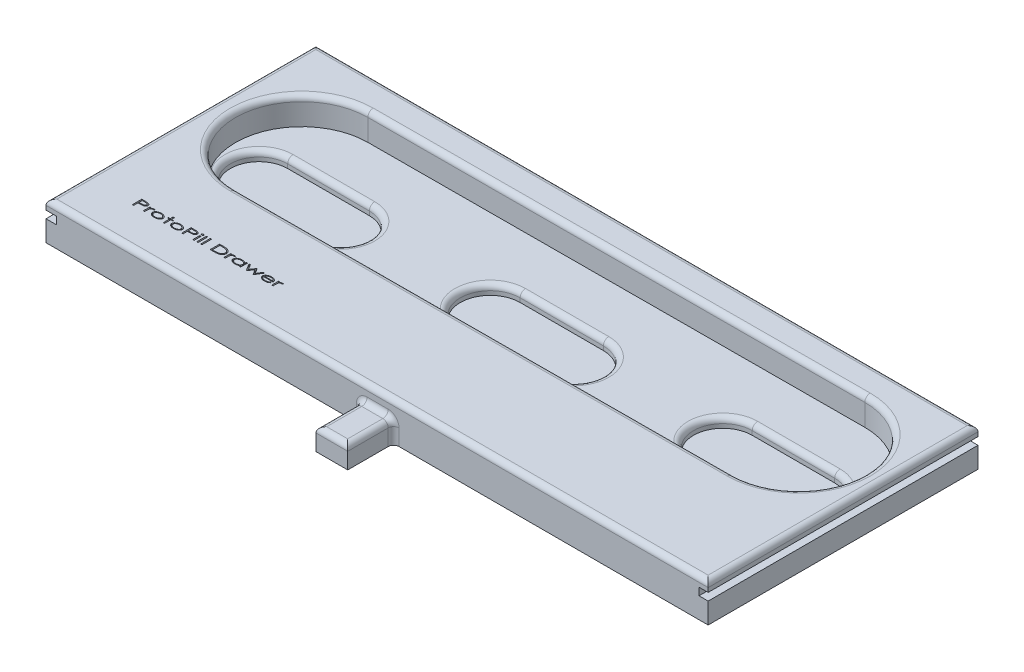
SolidWorks part; units mm, degrees
ref_plane "Front Plane" through (0, 0, 0) normal (0, 0, 1) x (1, 0, 0)
ref_plane "Top Plane" through (0, 0, 0) normal (0, 1, 0) x (1, 0, 0)
ref_plane "Right Plane" through (0, 0, 0) normal (1, 0, 0) x (0, 0, -1)
sketch "Sketch1" plane through (0, 0, 0) normal (0, 1, 0) x (1, 0, 0)
  line L2 (0.7909, -28.3198) -> (245.9852, -28.3198)
  line L4 (245.9852, 64.6802) -> (0.7909, 64.6802)
  line L6 (245.9852, 64.6802) -> (245.9852, -28.3198)
  line L7 (0.7909, 64.6802) -> (0.7909, -28.3198)
  point P0 (0, 0)
  dimension "D2" = 93
extrude "Boss-Extrude1" add sketch "Sketch1" along normal blind 14
sketch "Sketch3" plane through (0, 14, 0) normal (0, 1, 0) x (1, 0, 0)
  line L0 (37.1381, -19.9605) -> (-7.858, -19.9605) construction
  line L2 (37.1381, -19.9605) -> (37.1381, -24.4605) construction
  line L4 (37.1381, -19.9605) -> (123.1941, -19.9579) construction
  line L5 (123.6473, -19.9605) -> (210.1566, -19.9605) construction
  line L6 (210.1566, -19.9605) -> (210.1566, -24.4605) construction
  line L7 (123.6473, -19.9605) -> (123.6473, -24.4605) construction
  line L8 (37.1381, -19.9605) -> (37.1381, 7.1502) construction
  line L9 (123.6473, -19.9605) -> (123.6473, 8.5509) construction
  line L10 (210.1566, -19.9605) -> (210.1566, 7.8884) construction
  line L11 (0.0174, -19.9605) -> (247.1649, -19.9605)
  circle A2 centre (123.7727, -8.9393) radius 11.15
  circle A3 centre (37.3245, -8.6421) radius 11.15
  circle A4 centre (209.8985, -8.6813) radius 11.15
  dimension "D2" = 22.3
  dimension "D3" = 22.3
  dimension "D4" = 22.3
sketch "Sketch2" plane through (0, 0, 28.3198) normal (0, 0, 1) x (1, 0, 0)
  line L0 (0, 10.4529) -> (0, 7.6902)
  line L2 (0, 7.6902) -> (4.6941, 7.6902)
  line L3 (4.6941, 7.6902) -> (4.6941, 10.4529)
  line L5 (4.6941, 10.4529) -> (0, 10.4529)
extrude "Cut-Extrude1" cut sketch "Sketch2" against normal through all
ref_plane "Plane1" through (123.6473, 0, 0) normal (1, 0, 0) x (0, 0, -1)
mirror "Mirror5" about plane through (123.6473, 0, 0) normal (1, 0, 0) of "Cut-Extrude1"
sketch "Sketch7" plane through (0, 0, 28.3198) normal (0, 0, 1) x (1, 0, 0)
  line L0 (123.5912, 14) -> (123.6473, 0) construction
  line L1 (0.0174, 14) -> (247.1649, 14) construction
  line L2 (0.7909, 0) -> (245.9852, 0) construction
  line L3 (123.6473, -7.7) -> (123.6473, 7.7) construction
  line L9 (117.7248, 7.9809) -> (129.5137, 6.0191) construction
  line L10 (117.7248, 6.0191) -> (129.5137, 7.9809) construction
  line L11 (117.7248, 0) -> (129.5137, 0)
  line L12 (117.7248, 0) -> (117.7248, 7.9809)
  line L13 (117.7248, 7.9809) -> (129.5137, 7.9809)
  line L14 (129.5137, 0) -> (129.5137, 7.9809)
  point P8 (123.6193, 7)
extrude "Boss-Extrude2" add sketch "Sketch7" along normal blind 70
sketch "Sketch8" plane through (0, 0, 28.3198) normal (0, 0, 1) x (1, 0, 0)
  line L10 (245.9852, 10.4529) -> (245.9852, 14)
  line L12 (245.9852, 10.4529) -> (245.9852, 14)
  line L14 (245.9852, 14) -> (0.7909, 14)
  line L18 (0.7909, 14) -> (0.7909, 10.4529)
  line L19 (0.7909, 10.4529) -> (4.6941, 10.4529)
  line L20 (4.6941, 10.4529) -> (4.6941, 7.6902)
  line L21 (4.6941, 7.6902) -> (0.7909, 7.6902)
  line L22 (0.7909, 7.6902) -> (0.7909, 0)
  line L23 (0.7909, 0) -> (117.7248, 0)
  line L24 (117.7248, 0) -> (117.7248, 7.9809)
  line L30 (117.7248, 7.9809) -> (129.5137, 7.9809)
  line L31 (117.7248, 7.9809) -> (129.5137, 7.9809)
  line L34 (0.7909, 14) -> (0.7909, 10.4529)
  line L35 (0.7909, 10.4529) -> (4.6941, 10.4529)
  line L36 (4.6941, 10.4529) -> (4.6941, 7.6902)
  line L37 (4.6941, 7.6902) -> (0.7909, 7.6902)
  line L38 (0.7909, 7.6902) -> (0.7909, 0)
  line L39 (0.7909, 0) -> (117.7248, 0)
  line L40 (117.7248, 0) -> (117.7248, 7.9809)
  line L48 (129.5137, 7.9809) -> (129.5137, 0)
  line L49 (129.5137, 7.9809) -> (129.5137, 0)
  line L50 (129.5137, 0) -> (245.9852, 0)
  line L51 (129.5137, 0) -> (245.9852, 0)
  line L52 (245.9852, 0) -> (245.9852, 7.6902)
  line L53 (245.9852, 0) -> (245.9852, 7.6902)
  line L54 (245.9852, 7.6902) -> (242.6006, 7.6902)
  line L55 (245.9852, 7.6902) -> (242.6006, 7.6902)
  line L56 (242.6006, 7.6902) -> (242.6006, 10.4529)
  line L57 (242.6006, 7.6902) -> (242.6006, 10.4529)
  line L58 (242.6006, 10.4529) -> (245.9852, 10.4529)
  line L59 (242.6006, 10.4529) -> (245.9852, 10.4529)
  line L60 (245.9852, 14) -> (0.7909, 14)
  dimension "D1" = 0
extrude "Boss-Extrude3" add sketch "Sketch8" along normal blind 53
sketch "Sketch9" plane through (0, 14, 0) normal (0, 1, 0) x (1, 0, 0)
  line L0 (32.277, -18.0846) -> (215.6701, -17.457) construction
  line L3 (32.193, 6.4621) -> (215.5861, 7.0898)
  line L4 (32.361, -42.6314) -> (215.7541, -42.0037)
  arc A0 (32.193, 6.4621) -> (32.361, -42.6314) centre (32.277, -18.0846) ccw
  arc A1 (215.7541, -42.0037) -> (215.5861, 7.0898) centre (215.6701, -17.457) ccw
  point P6 (123.9735, -17.7708)
extrude "Cut-Extrude2" cut sketch "Sketch9" against normal blind 10
sketch "Sketch10" plane through (0, 4, 0) normal (0, 1, 0) x (1, 0, 0)
  line L0 (22.2559, -23.9029) -> (52.4711, -23.9029) construction
  line L1 (22.2559, -13.2713) -> (52.4711, -13.2713)
  line L2 (22.2559, -34.5345) -> (52.4711, -34.5345)
  line L3 (108.2536, -24.2865) -> (139.0697, -24.2865) construction
  line L4 (108.2536, -13.2003) -> (139.0697, -13.2003)
  line L5 (108.2536, -35.3728) -> (139.0697, -35.3728)
  line L6 (193.8044, -23.6865) -> (224.3383, -23.6865) construction
  line L7 (193.8044, -12.8155) -> (224.3383, -12.8155)
  line L8 (193.8044, -34.5575) -> (224.3383, -34.5575)
  arc A0 (22.2559, -13.2713) -> (22.2559, -34.5345) centre (22.2559, -23.9029) ccw
  arc A1 (52.4711, -34.5345) -> (52.4711, -13.2713) centre (52.4711, -23.9029) ccw
  arc A2 (108.2536, -13.2003) -> (108.2536, -35.3728) centre (108.2536, -24.2865) ccw
  arc A3 (139.0697, -35.3728) -> (139.0697, -13.2003) centre (139.0697, -24.2865) ccw
  arc A4 (193.8044, -12.8155) -> (193.8044, -34.5575) centre (193.8044, -23.6865) ccw
  arc A5 (224.3383, -34.5575) -> (224.3383, -12.8155) centre (224.3383, -23.6865) ccw
  point P2 (37.3635, -23.9029)
  point P9 (123.6616, -24.2865)
  point P16 (209.0714, -23.6865)
extrude "Cut-Extrude4" cut sketch "Sketch10" against normal blind 3.5
fillet "Fillet2" radius 2 4 edges at (240.2169, 14, 17.373) (124.0576, 14, 42.3176) (7.7302, 14, 18.1686) (123.8895, 14, -6.776)
fillet "Fillet3" radius 2 12 edges at (235.2093, 4, 23.6865) (209.0714, 4, 34.5575) (182.9335, 4, 23.6865) (150.1559, 4, 24.2865) (123.6616, 4, 35.3728) (97.1674, 4, 24.2865) (63.1027, 4, 23.9029) (37.3635, 4, 34.5345) (11.6243, 4, 23.9029) (209.0714, 4, 12.8155) (123.6616, 4, 13.2003) (37.3635, 4, 13.2713)
sketch "Sketch11" plane through (0, 14, 0) normal (0, 1, 0) x (1, 0, 0)
  line L0 (0.7909, 18.6064) -> (245.9852, 18.6064)
  line L1 (0.7909, 64.6802) -> (0.7909, -81.3198) construction
  line L2 (245.9852, -81.3198) -> (245.9852, 64.6802) construction
  line L3 (245.9852, 18.6064) -> (245.9852, 64.6802)
  line L4 (245.9852, 64.6802) -> (0.7909, 64.6802)
  line L5 (0.7909, 64.6802) -> (0.7909, 18.6064)
extrude "Cut-Extrude5" cut sketch "Sketch11" against normal through all
fillet "Fillet4" radius 2 10 edges at (117.7248, 3.9904, 81.3198) (129.5137, 3.9904, 81.3198) (123.6193, 7.9809, 98.3198) (117.7248, 7.9809, 89.8198) (123.6193, 7.9809, 81.3198) (129.5137, 7.9809, 89.8198) (245.9852, 14, 31.3567) (123.3881, 14, 81.3198) (0.7909, 14, 31.3567) (123.3881, 14, -18.6064)
sketch "Sketch12" plane through (0, 0, 0) normal (0, -1, 0) x (1, 0, 0)
  circle A0 centre (79.2049, -2.6546) radius 3.025
  circle A2 centre (79.2049, 6.3419) radius 3.025
  circle A10 centre (169.8585, 5.9307) radius 3.025
  circle A11 centre (169.8585, -2.6546) radius 3.025
extrude "Cut-Extrude6" cut sketch "Sketch12" against normal blind 2
sketch "Sketch13" plane through (0, 14, 0) normal (0, 1, 0) x (1, 0, 0)
  text T0 "ProtoPill Drawer" font "Century Gothic" height 3.5
extrude "Cut-Extrude7" cut sketch "Sketch13" against normal blind 2
sketch "Sketch14" plane through (0, 0, 0) normal (0, -1, 0) x (1, 0, 0)
  line L0 (76.1475, 6.1393) -> (79.1725, 12.8178)
  line L1 (79.1725, 12.8178) -> (82.1975, 6.1393)
  line L2 (82.1975, 6.1393) -> (76.1475, 6.1393)
  line L3 (76.1475, -2.8572) -> (79.1725, -9.5356)
  line L4 (79.1725, -9.5356) -> (82.1975, -2.8572)
  line L5 (82.1975, -2.8572) -> (76.1475, -2.8572)
  line L6 (166.8011, 5.7281) -> (169.8261, 12.4066)
  line L7 (169.8261, 12.4066) -> (172.8511, 5.7281)
  line L8 (172.8511, 5.7281) -> (166.8011, 5.7281)
  line L9 (166.8011, -2.8572) -> (169.8261, -9.5356)
  line L10 (169.8261, -9.5356) -> (172.8511, -2.8572)
  line L11 (172.8511, -2.8572) -> (166.8011, -2.8572)
extrude "Cut-Extrude8" cut sketch "Sketch14" against normal blind 2
sketch "Sketch15" plane through (0, 14, 0) normal (0, 1, 0) x (1, 0, 0)
  line L2 (146.7092, -47.8489) -> (134.6091, -54.4141)
  line L3 (146.7092, -47.8489) -> (146.7092, -74.4208)
  line L4 (146.7092, -74.4208) -> (134.6091, -67.8555)
